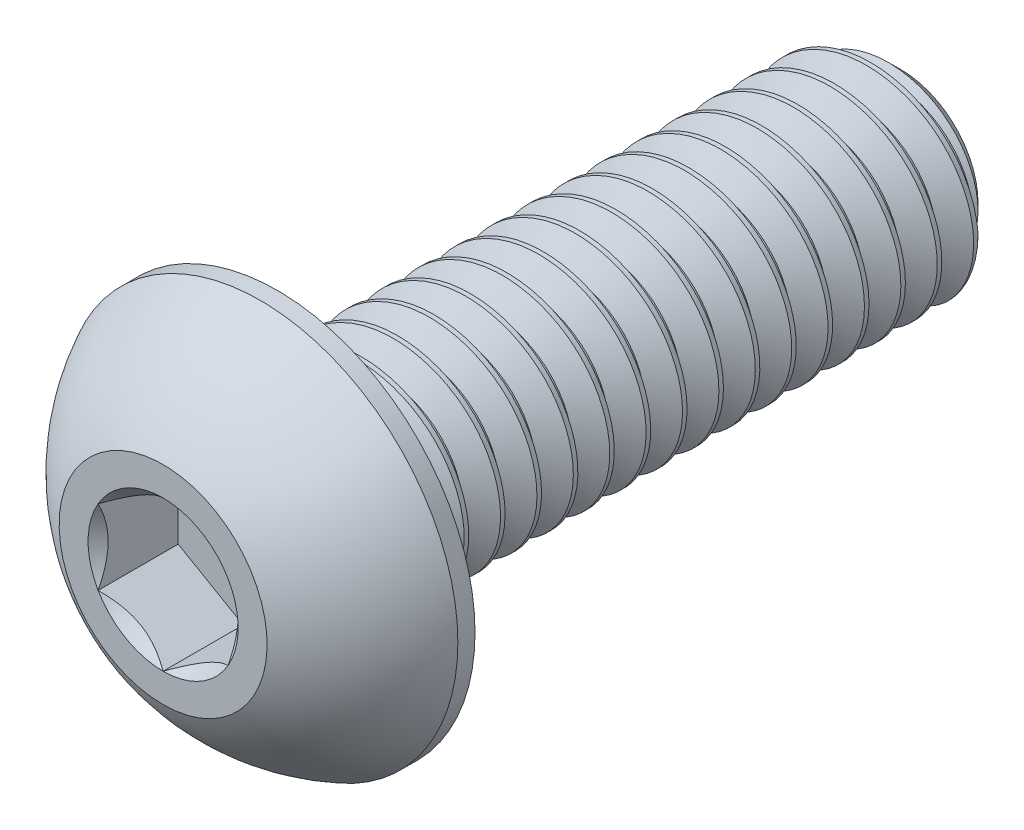
SolidWorks part; units mm, degrees
ref_plane "Front" through (0, 0, 0) normal (0, 0, 1) x (1, 0, 0)
ref_plane "Top" through (0, 0, 0) normal (0, 1, 0) x (1, 0, 0)
ref_plane "Right" through (0, 0, 0) normal (1, 0, 0) x (0, 0, -1)
sketch "Sketch1" plane through (0, 0, 0) normal (1, 0, 0) x (0, 0, -1)
  line L2 (2.2, 2) -> (14.2, 2)
  line L3 (14.2, 2) -> (14.2, 0)
  line L4 (14.2, 0) -> (2.2, 0)
  line L6 (1.87, 3.8) -> (2.2, 3.8) construction
  line L7 (14.2, 2) -> (14.2, -2) construction
  line L8 (0, 0) -> (2.2, 0) construction
  line L9 (2.2, 3.8) -> (2.2, -3.8) construction
  line L11 (2.2, 2) -> (2.2, 0)
  line L13 (0, 1.25) -> (0, -1.25) construction
  line L14 (0, 1.25) -> (0, 2) construction
  arc A3 (0, 2) -> (1.87, 3.8) centre (3.7264, 0) cw construction
  dimension "D1" = 0.33
revolve "Revolve1" add sketch "Sketch1" angle 360 mid plane about L4
sketch "Sketch3" plane through (0, 0, -14.2) normal (0, 0, -1) x (-1, 0, 0)
  circle A0 centre (0, 0) radius 2
curve "Helix/Spiral1" pitch 0.7 height 14.2 radius 2 centre (0, 0, -14.2) axis (0, 0, 1) start towards (0, 1, 0)
sketch "Sketch2" plane through (0, 0, 0) normal (1, 0, 0) x (0, 0, -1)
  line L0 (14.2, 2) -> (14.8125, 2)
  line L1 (14.8125, 2) -> (14.55, 1.5453)
  line L2 (14.55, 1.5453) -> (14.4625, 1.5453)
  line L3 (14.4625, 1.5453) -> (14.2, 2)
  line L4 (14.3313, 1.7727) -> (14.6813, 1.7727) construction
  dimension "D1" = 60
  dimension "D2" = 0.0875
  dimension "D3" = 0.35
chamfer "Chamfer1" distance 0.525 angle 45 1 edges at (0, 2, -14.2)
sweep "Cut-Sweep1" cut profiles "Sketch2" path "Helix/Spiral1" align with end faces yes
sketch "Sketch7" plane through (0, 0, 0) normal (1, 0, 0) x (0, 0, -1)
  line L6 (1.87, 3.8) -> (2.2, 3.8) construction
  line L8 (0, 0) -> (2.2, 0) construction
  line L11 (2.2, 3.8) -> (2.2, -3.8) construction
  line L12 (1.87, 3.8) -> (2.2, 3.8)
  line L13 (0, 0) -> (2.2, 0)
  line L14 (0, 1.25) -> (0, -1.25) construction
  line L15 (2.2, 3.8) -> (2.2, 0)
  line L16 (0, 2) -> (0, 0)
  arc A2 (1.87, 3.8) -> (0, 2) centre (3.7264, 0) ccw construction
  arc A3 (1.87, 3.8) -> (0, 2) centre (3.7264, 0) ccw
revolve "Revolve2" add sketch "Sketch7" angle 360 mid plane about L13
sketch "Sketch5" plane through (0, 0, 0) normal (0, 0, 1) x (1, 0, 0)
  line L1 (1.25, -0.7217) -> (1.25, 0.7217)
  line L2 (1.25, 0.7217) -> (0, 1.4434)
  line L3 (0, 1.4434) -> (-1.25, 0.7217)
  line L4 (-1.25, 0.7217) -> (-1.25, -0.7217)
  line L5 (-1.25, -0.7217) -> (0, -1.4434)
  line L6 (0, -1.4434) -> (1.25, -0.7217)
  circle A0 centre (0, 0) radius 1.25 construction
extrude "Cut-Extrude2" cut sketch "Sketch5" against normal blind 1.54
sketch "Sketch6" plane through (0, 0, 0) normal (0, 0, 1) x (1, 0, 0)
  circle A0 centre (0, 0) radius 1.4434
extrude "Cut-Extrude3" cut sketch "Sketch6" against normal blind 1.54 draft 45
sketch "Sketch9" [suppressed] plane through (0, 0, -2.2) normal (0, 0, 1) x (1, 0, 0)
  circle A2 centre (0, 0) radius 1.5
extrude "Boss-Extrude2" [suppressed] add sketch "Sketch9" against normal offset from surface (20 mm away) 32 up to face at (0, 1.475, -14.2)
sketch "Sketch10" plane through (0, 0, 0) normal (1, 0, 0) x (0, 0, -1)
  line L0 (14.2, 2) -> (14.2, -2) construction
  point P0 (13.15, -2)
  dimension "D1" = 1.05
equation "\"D3@Helix/Spiral1\" = \"Lg@Sketch1\" + \"Head Ht@Sketch1\""
equation "\"D2@Sketch2\" = \"D4@Helix/Spiral1\" * .125"
equation "\"D3@Sketch2\" = \"D4@Helix/Spiral1\" * .5"
equation "\"D1@Chamfer1\" = \"D4@Helix/Spiral1\" * .75"
equation "\"D1@Cut-Extrude2\" = \"Head Ht@Sketch1\" * .7"
equation "\"D1@Sketch1\" = \"Head Ht@Sketch1\" * .15"
equation "\"D1@Sketch10\" = \"D4@Helix/Spiral1\" * 1.5"
equation "\"D1@Cut-Extrude3\" = \"D1@Cut-Extrude2\""
